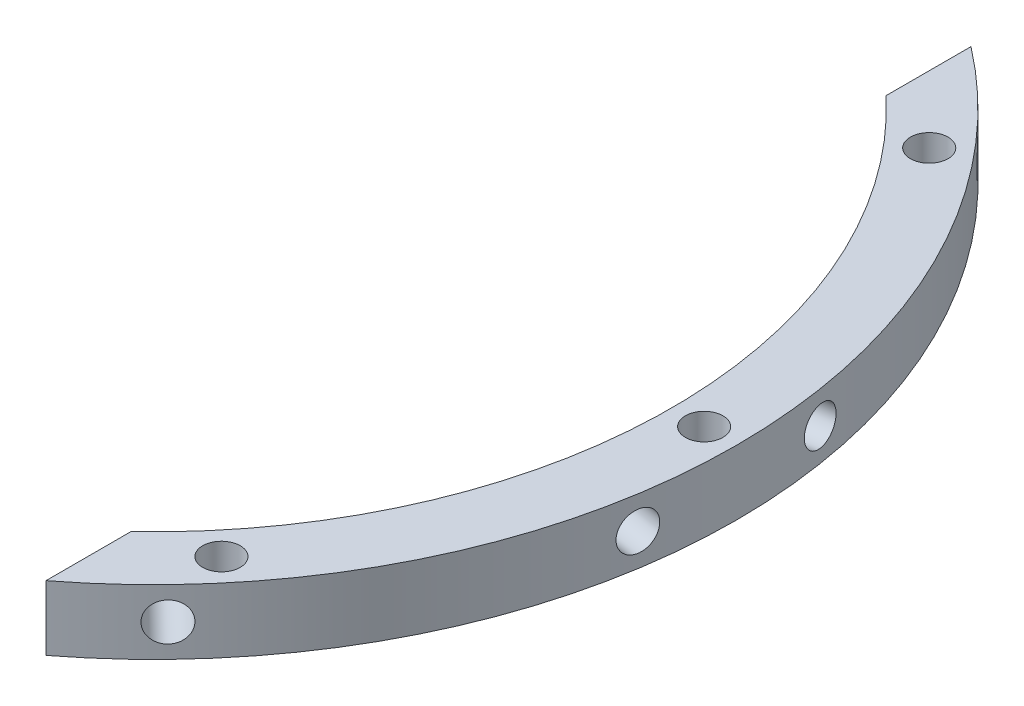
SolidWorks part; units mm, degrees
ref_plane "Спереди" through (0, 0, 0) normal (0, 0, 1) x (1, 0, 0)
ref_plane "Сверху" through (0, 0, 0) normal (0, 1, 0) x (1, 0, 0)
ref_plane "Справа" through (0, 0, 0) normal (1, 0, 0) x (0, 0, -1)
sketch "Эскиз1" plane through (0, 0, 0) normal (0, 1, 0) x (1, 0, 0)
  line L0 (27.3954, 29.146) -> (27.3954, 35.7)
  line L1 (27.3954, -35.7) -> (27.3954, -29.146)
  arc A0 (27.3954, 35.7) -> (27.3954, -35.7) centre (0, 0) cw
  arc A1 (27.3954, 29.146) -> (27.3954, -29.146) centre (0, 0) cw
  point P6 (0, 0)
  point P7 (0, 0)
  dimension "D3" = 45
  dimension "D2" = 5
  dimension "D1" = 71.4
extrude "Бобышка-Вытянуть1" add sketch "Эскиз1" along normal blind 5
sketch "Эскиз2" plane through (0, 5, 0) normal (0, 1, 0) x (1, 0, 0)
  line L0 (-1000, 0) -> (49000, 0) construction
  line L1 (0, 0) -> (32.5569, 27.3185) construction
  circle A0 centre (0, 0) radius 42.5 construction
  circle A1 centre (42.5, 0) radius 1.45
  circle A2 centre (32.5569, 27.3185) radius 1.45
  circle A4 centre (32.5569, -27.3185) radius 1.45
  dimension "D1" = 85
  dimension "D2" = 40
  dimension "D3" = 2.9
extrude "Вырез-Вытянуть1" cut sketch "Эскиз2" against normal blind 5
ref_axis "Ось1" through (0, -0.25, 0) along (0, 1, 0)
ref_plane "Плоскость4" through (0, 0, 0) normal (0.7193, 0, 0.6947) x (0, 1, 0)
sketch "Эскиз3" plane through (0, 0, 0) normal (0.7193, 0, 0.6947) x (0, 1, 0)
  line L1 (-0.25, 0) -> (5.25, 0) construction
  line L2 (0, 6.65) -> (0, -45) construction
  circle A0 centre (2.5, 0) radius 1.475
  point P1 (2.4472, 0)
  point P5 (0, 0)
  dimension "D1" = 2.95
  dimension "D2" = 2.5
extrude "Вырез-Вытянуть2" cut sketch "Эскиз3" along normal blind 46
pattern_circular "Круговой массив1" count 2 every 35 about axis through (0, -0.25, 0) along (0, 1, 0) of "Вырез-Вытянуть2"
mirror "Зеркальное отражение1" about plane through (0, 0, 0) normal (0, 0, 1) of "Вырез-Вытянуть2", "Круговой массив1"
